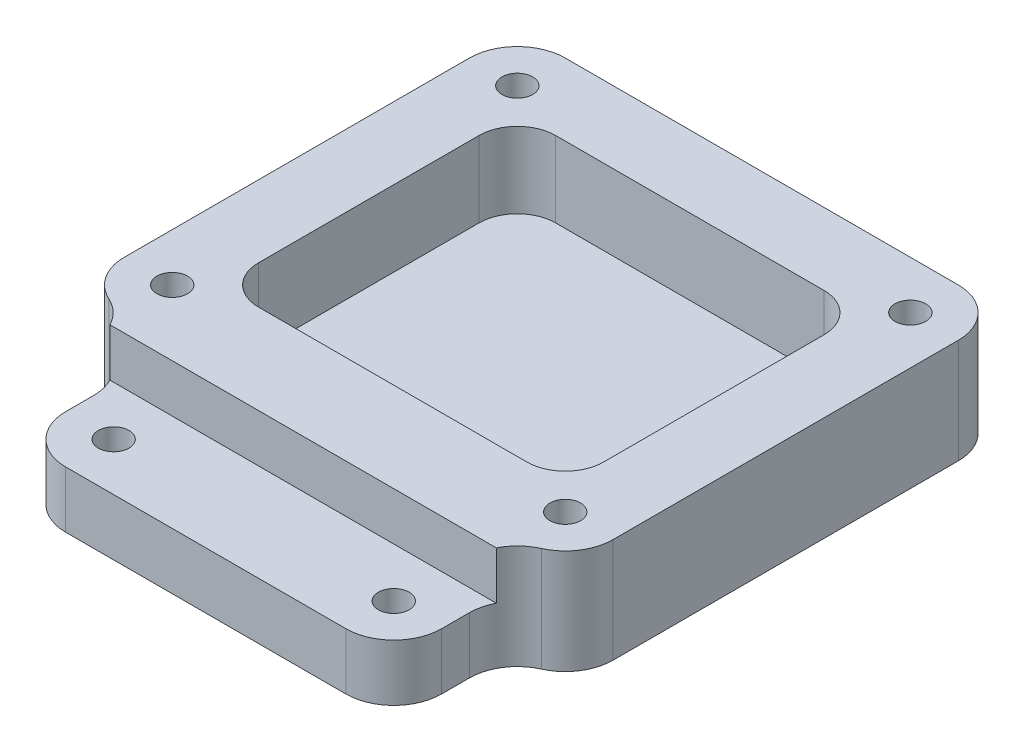
SolidWorks part; units mm, degrees
material "ナイロン"
ref_plane "正面" through (0, 0, 0) normal (0, 0, 1) x (1, 0, 0)
ref_plane "平面" through (0, 0, 0) normal (0, 1, 0) x (1, 0, 0)
ref_plane "右側面" through (0, 0, 0) normal (1, 0, 0) x (0, 0, -1)
sketch "ｽｹｯﾁ1" plane through (0, 0, 0) normal (0, 1, 0) x (1, 0, 0)
  line L0 (0, 23) -> (0, -23) construction
  line L1 (-25.5, -23) -> (25.5, -23)
  line L2 (-25.5, -23) -> (-25.5, 23)
  line L3 (-25.5, 23) -> (25.5, 23)
  line L4 (25.5, -23) -> (25.5, 23)
  line L5 (-25.5, -23) -> (25.5, 23) construction
  line L6 (-25.5, 23) -> (25.5, -23) construction
  line L7 (-25.5, 0) -> (25.5, 0) construction
  line L8 (0, -23) -> (0, -29) construction
  line L10 (-19.61, -35) -> (19.61, -35)
  line L11 (-19.61, -35) -> (-19.61, -23)
  line L12 (-19.61, -23) -> (19.61, -23)
  line L13 (19.61, -35) -> (19.61, -23)
  line L14 (-19.61, -35) -> (19.61, -23) construction
  line L15 (-19.61, -23) -> (19.61, -35) construction
  circle A0 centre (20.5, 18) radius 1.6
  circle A1 centre (-20.5, 18) radius 1.6
  circle A2 centre (-20.5, -18) radius 1.6
  circle A3 centre (20.5, -18) radius 1.6
  circle A4 centre (14.61, -30) radius 1.6
  circle A5 centre (-14.61, -30) radius 1.6
  point P0 (0, 0)
  dimension "D1" = 5
  dimension "D2" = 5
  dimension "D3" = 3.2
  dimension "D4" = 41
  dimension "D5" = 36
  dimension "D6" = 29.22
  dimension "D8" = 3.2
  dimension "D10" = 5
  dimension "D7" = 5
  dimension "D9" = 12
extrude "ﾎﾞｽ - 押し出し1" add sketch "ｽｹｯﾁ1" along normal blind 10.9 contours L1 L4 L3 L2 A1 A0 A2 A3 | L10 L13 L1 L11 A4 A5 region at (0, 0, 0) region at (0, 0, 28.9646)
sketch "ｽｹｯﾁ2" plane through (0, 10.9, 0) normal (0, 1, 0) x (1, 0, 0)
  line L5 (-14.61, -30) -> (14.61, -30) construction
  line L6 (19.61, -35) -> (19.61, -23) construction
  line L7 (-19.61, -35.15) -> (19.61, -35.15)
  line L8 (-19.61, -35.15) -> (-19.61, -24.85)
  line L9 (-19.61, -24.85) -> (19.61, -24.85)
  line L10 (19.61, -35.15) -> (19.61, -24.85)
  line L11 (-19.61, -35.15) -> (19.61, -24.85) construction
  line L12 (-19.61, -24.85) -> (19.61, -35.15) construction
  point P2 (0, -30)
  dimension "10.3" = 10.3
extrude "ｶｯﾄ - 押し出し1" cut sketch "ｽｹｯﾁ2" against normal blind 5
fillet "ﾌｨﾚｯﾄ1" radius 5 6 edges at (-25.5, 5.45, 23) (-25.5, 5.45, -23) (25.5, 5.45, -23) (25.5, 5.45, 23) (19.61, 2.95, 35) (-19.61, 2.95, 35)
sketch "ｽｹｯﾁ3" plane through (0, 10.9, 0) normal (0, 1, 0) x (1, 0, 0)
  line L5 (-20.5, 23) -> (20.5, 23) construction
  line L6 (-18, -15.5) -> (18, -15.5)
  line L8 (-18, -15.5) -> (-18, 15.5)
  line L9 (-18, 15.5) -> (18, 15.5)
  line L10 (18, -15.5) -> (18, 15.5)
  line L11 (-18, -15.5) -> (18, 15.5) construction
  line L12 (-18, 15.5) -> (18, -15.5) construction
  line L13 (25.5, -18) -> (25.5, 18) construction
  point P0 (0, 0)
  dimension "D1" = 7.5
  dimension "D2" = 7.5
extrude "ｶｯﾄ - 押し出し2" cut sketch "ｽｹｯﾁ3" against normal blind 7.9
fillet "ﾌｨﾚｯﾄ3" radius 4 4 edges at (18, 6.95, 15.5) (18, 6.95, -15.5) (-18, 6.95, 15.5) (-18, 6.95, -15.5)
fillet "ﾌｨﾚｯﾄ2" radius 5 2 edges at (-19.61, 5.45, 23) (19.61, 5.45, 23)
